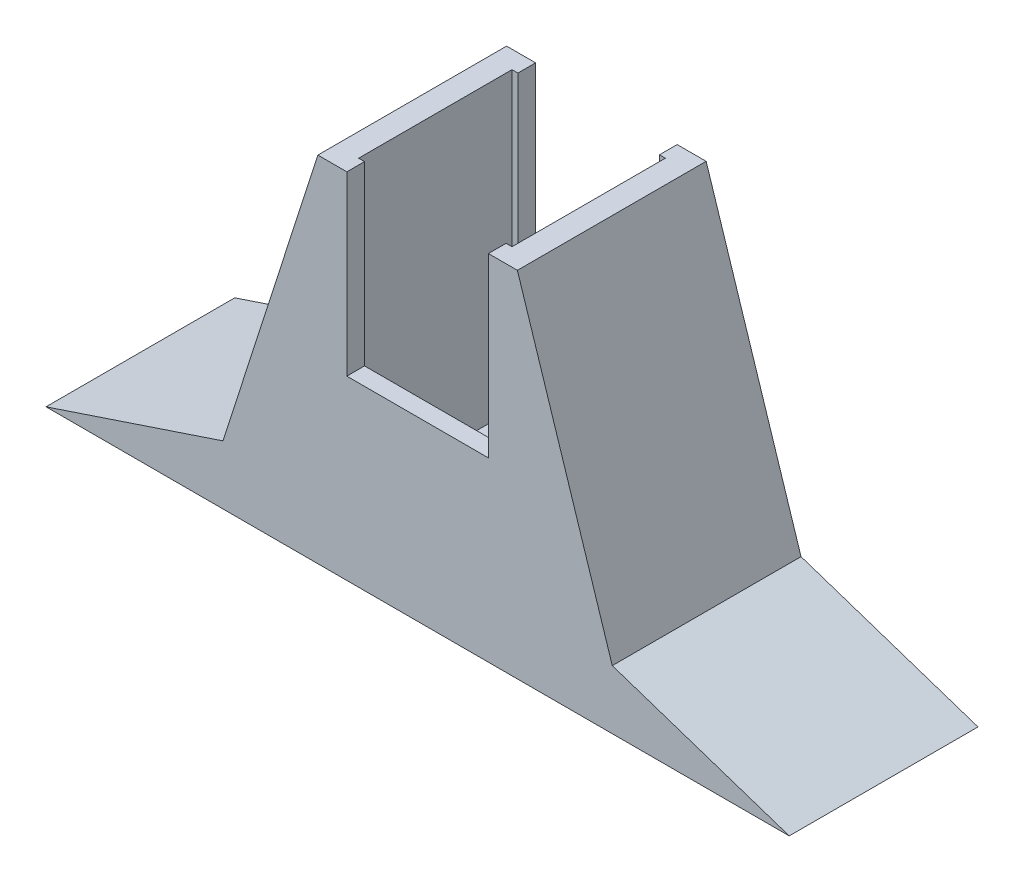
SolidWorks part; units mm, degrees
ref_plane "정면" through (0, 0, 0) normal (0, 0, 1) x (1, 0, 0)
ref_plane "윗면" through (0, 0, 0) normal (0, 1, 0) x (1, 0, 0)
ref_plane "우측면" through (0, 0, 0) normal (1, 0, 0) x (0, 0, -1)
sketch "스케치1" plane through (0, 0, 0) normal (0, 0, 1) x (1, 0, 0)
  line L0 (0, 0) -> (0, 30) construction
  line L1 (31.5, 0) -> (-31.5, 0)
  line L2 (-31.5, 0) -> (-16.5, 5)
  line L3 (31.5, 0) -> (16.5, 5)
  line L4 (-16.5, 5) -> (-11.5, 10)
  line L5 (16.5, 5) -> (11.5, 10)
  line L6 (-11.5, 10) -> (-8.4575, 30)
  line L7 (11.5, 10) -> (8.4575, 30)
  line L8 (-8.4575, 30) -> (8.4575, 30)
  dimension "D1" = 63
  dimension "D2" = 30
  dimension "D3" = 15
  dimension "D4" = 5
  dimension "D5" = 5
  dimension "D6" = 5
extrude "보스-돌출2" add sketch "스케치1" along normal blind 16 contours L8 L7 L5 L3 L1 L2 L4 L6
sketch "스케치3" plane through (0, 30, 0) normal (0, 1, 0) x (1, 0, 0)
  line L0 (0, 0) -> (0, -16) construction
  line L1 (-8.4575, -16) -> (8.4575, -16) construction
  line L2 (-8.4575, -8) -> (8.4575, -8) construction
  line L3 (-8.4575, -16) -> (-8.4575, 0) construction
  line L4 (8.4575, -16) -> (8.4575, 0) construction
  line L6 (-6.5, -14.5) -> (6.5, -14.5)
  line L7 (-6.5, -14.5) -> (-6.5, -1.5)
  line L8 (-6.5, -1.5) -> (6.5, -1.5)
  line L9 (6.5, -14.5) -> (6.5, -1.5)
  line L10 (0, -1.5) -> (0, -14.5) construction
  line L11 (-6.5, -8) -> (6.5, -8) construction
  point P11 (0, -8)
  dimension "D1" = 13
  dimension "D2" = 13
extrude "컷-돌출3" cut sketch "스케치3" against normal blind 25 contours L9 L8 L7 L6
sketch "스케치6" plane through (0, 0, 16) normal (0, 0, 1) x (1, 0, 0)
  line L0 (0, 0) -> (0, 30) construction
  line L1 (-8.4575, 30) -> (8.4575, 30) construction
  line L2 (0, 30) -> (0, 15) construction
  line L3 (0, 15) -> (-10.7394, 15) construction
  line L4 (-11.5, 10) -> (-8.4575, 30) construction
  line L5 (-10.7394, 15) -> (10.7394, 15) construction
  line L6 (11.5, 10) -> (8.4575, 30) construction
  line L8 (0, 15) -> (6, 15)
  line L9 (0, 15) -> (0, 30)
  line L10 (0, 30) -> (6, 30)
  line L11 (6, 15) -> (6, 30)
  line L12 (0, 15) -> (-6, 15)
  line L13 (0, 15) -> (0, 30)
  line L14 (0, 30) -> (-6, 30)
  line L15 (-6, 15) -> (-6, 30)
  line M10 (8.4575, 30) -> (-8.4575, 30)
  dimension "D1" = 6
  dimension "D2" = 6
extrude "컷-돌출4" cut sketch "스케치6" against normal blind 25 contours L8 L11 L9 M10 | L15 L12 L9 M10 region at (3, 22.5, 16) region at (-3, 22.5, 16)
sketch "스케치7" plane through (0, 0, 16) normal (0, 0, 1) x (1, 0, 0)
  line L0 (-16.5, 5) -> (-8.4575, 30)
  line L1 (8.4575, 30) -> (11.5, 10)
  line L2 (-16.5, 5) -> (-11.5, 10)
  line L3 (-11.5, 10) -> (-8.4575, 30)
  line L4 (11.5, 10) -> (16.5, 5)
  line L5 (16.5, 5) -> (8.4575, 30)
extrude "보스-돌출3" add sketch "스케치7" against normal blind 16
